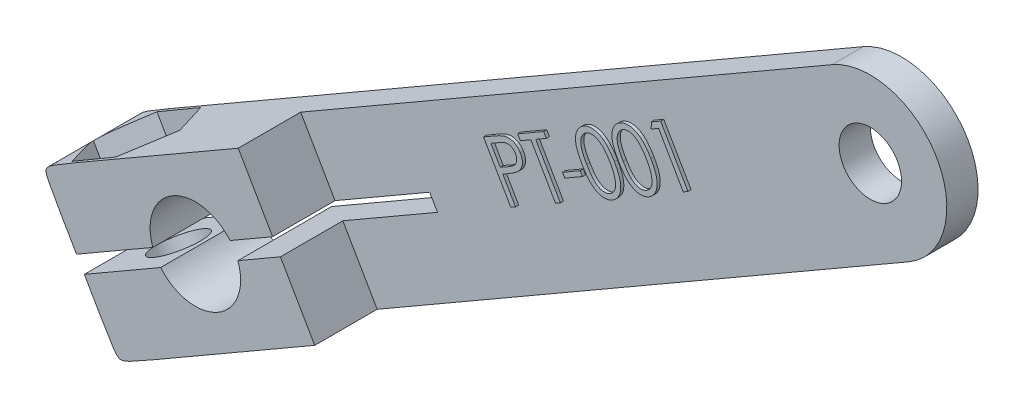
SolidWorks part; units mm, degrees
ref_plane "Piano frontale" through (0, 0, 0) normal (0, 0, 1) x (1, 0, 0)
ref_plane "Piano superiore" through (0, 0, 0) normal (0, 1, 0) x (1, 0, 0)
ref_plane "Piano destro" through (0, 0, 0) normal (1, 0, 0) x (0, 0, -1)
sketch "Schizzo1" plane through (0, 0, 0) normal (0, 0, 1) x (1, 0, 0)
  line L0 (0, 0) -> (0, 55.2) construction
  line L1 (0, 55.2) -> (0, 45.3)
  line L2 (0, 0) -> (39.231, 22.65) construction
  line L3 (0, 45.3) -> (39.231, 22.65) construction
  line L4 (0, 0) -> (39.231, 22.65) construction
  line L5 (-2.45, 4.2435) -> (36.781, 26.8935)
  line L6 (2.45, -4.2435) -> (41.681, 18.4065)
  circle A0 centre (0, 0) radius 2.9
  circle A1 centre (39.231, 22.65) radius 2
  arc A2 (-2.45, 4.2435) -> (2.45, -4.2435) centre (0, 0) ccw
  arc A3 (41.681, 18.4065) -> (36.781, 26.8935) centre (39.231, 22.65) ccw
  point P7 (19.6155, 11.325)
extrude "Estrusione-Estrusione1" add sketch "Schizzo1" along normal blind 2 contours L6 A3 L5 A2 A0 A1 region at (20.1812, 11.6516, 0)
sketch "Schizzo2" plane through (0, 0, 2) normal (0, 0, 1) x (1, 0, 0)
  line L0 (-2.45, 4.2435) -> (-12.8423, -1.7565) construction
  line L1 (-12.8423, -1.7565) -> (-2.45, 4.2435)
  line L2 (-12.8423, -1.7565) -> (-7.9423, -10.2435)
  line L4 (-7.9423, -10.2435) -> (2.45, -4.2435)
  line L5 (41.681, 18.4065) -> (2.45, -4.2435)
  line L6 (41.681, 18.4065) -> (2.45, -4.2435)
  line L7 (-2.45, 4.2435) -> (36.781, 26.8935)
  line L8 (-2.45, 4.2435) -> (36.781, 26.8935)
  line L9 (-2.45, 4.2435) -> (2.7462, 7.2435)
  line L10 (2.7462, 7.2435) -> (7.6462, -1.2435)
  line L11 (7.6462, -1.2435) -> (2.45, -4.2435)
  arc A0 (-2.45, 4.2435) -> (2.45, -4.2435) centre (0, 0) ccw
  arc A2 (41.681, 18.4065) -> (36.781, 26.8935) centre (39.231, 22.65) ccw
  arc A3 (41.681, 18.4065) -> (36.781, 26.8935) centre (39.231, 22.65) ccw
  arc A4 (-2.45, 4.2435) -> (2.45, -4.2435) centre (0, 0) ccw
  point P13 (0, 0)
  point P14 (0, 0)
  circle M11 centre (0, 0) radius 2.9
  line M13 (2.45, -4.2435) -> (41.681, 18.4065)
  arc M16 (-2.45, 4.2435) -> (2.45, -4.2435) centre (0, 0) ccw
extrude "Estrusione-Estrusione2" add sketch "Schizzo2" along normal blind 4 and the other way blind 2 contours L2 L4 L1 M16 | L8 A4 L4 L10 M16 M13 M11 region at (-6.799, -3.9254, 2) region at (0.2354, 5.5923, 2)
sketch "Schizzo3" plane through (0, 0, 6) normal (0, 0, 1) x (1, 0, 0)
  line L0 (0, 0) -> (-10.3923, -6) construction
  line L1 (-12.8423, -1.7565) -> (-7.9423, -10.2435) construction
  line L6 (-10.3923, -6) -> (-10.1423, -6.433)
  line L7 (-10.1423, -6.433) -> (11.5083, 6.067)
  line L8 (-10.1423, -6.433) -> (-10.6423, -5.567)
  line L9 (11.5083, 6.067) -> (11.0083, 6.933)
  line L10 (-10.6423, -5.567) -> (11.0083, 6.933)
  point P11 (0, 0)
  point P12 (0, 0)
  point P13 (0, 0)
  point P14 (0, 0)
  point P15 (0, 0)
  line M9 (-12.8423, -1.7565) -> (-7.9423, -10.2435)
  line M11 (7.6462, -1.2435) -> (2.7462, 7.2435)
  circle M13 centre (0, 0) radius 2.9
extrude "Taglio-Estrusione1" cut sketch "Schizzo3" against normal blind 6 contours L10 L7 L9 M11 | L10 L7 M13 M11 | L0 L7 M13 M9 | L0 L10 M13 M9 region at (-6.3205, -3.9381, 6) region at (-6.5707, -3.5047, 6) region at (3.8475, 2.2214, 6) region at (8.2272, 4.75, 6)
sketch "Schizzo4" plane through (2.45, -4.2435, 0) normal (0.5, -0.866, 0) x (0.866, 0.5, 0)
  line L0 (-12, 3) -> (-5, 3) construction
  line L1 (-12, 0) -> (-12, 6) construction
  circle A0 centre (-5, 3) radius 1.6
extrude "Taglio-Estrusione2" cut sketch "Schizzo4" against normal blind 13
sketch "Schizzo5" plane through (-2.45, 4.2435, 0) normal (-0.5, 0.866, 0) x (0.866, 0.5, 0)
  line L1 (-6.629, -0.2676) -> (-8.1808, -3.0445)
  line L2 (-8.1808, -3.0445) -> (-6.5518, -5.7769)
  line L3 (-6.5518, -5.7769) -> (-3.371, -5.7324)
  line L4 (-3.371, -5.7324) -> (-1.8192, -2.9555)
  line L5 (-1.8192, -2.9555) -> (-3.4482, -0.2231)
  line L6 (-3.4482, -0.2231) -> (-6.629, -0.2676)
  circle A0 centre (-5, -3) radius 3.1811 construction
extrude "Taglio-Estrusione3" cut sketch "Schizzo5" against normal blind 2.4
sketch "Schizzo6" plane through (-10.3923, -6, 0) normal (-0.866, -0.5, 0) x (0, 0, 1)
  line L0 (6, 4.9) -> (6, 0.5)
  line L1 (6, 4.9) -> (6, 0.5)
  line L2 (6, 0.5) -> (2, 0.5)
  line L3 (6, 0.5) -> (2, 0.5)
  line L4 (2, 0.5) -> (2, -0.5)
  line L5 (2, 0.5) -> (2, -0.5)
  line L6 (2, -0.5) -> (6, -0.5)
  line L7 (2, -0.5) -> (6, -0.5)
  line L8 (6, -0.5) -> (6, -4.9)
  line L9 (6, -0.5) -> (6, -4.9)
  line L10 (6, -4.9) -> (2, -4.9)
  line L11 (6, -4.9) -> (2, -4.9)
  line L12 (2, -4.9) -> (0, -4.9)
  line L13 (2, -4.9) -> (0, -4.9)
  line L14 (0, -4.9) -> (0, 4.9)
  line L15 (0, -4.9) -> (0, 4.9)
  line L16 (0, 4.9) -> (2, 4.9)
  line L17 (0, 4.9) -> (2, 4.9)
  line L18 (2, 4.9) -> (6, 4.9)
  line L19 (2, 4.9) -> (6, 4.9)
extrude "Taglio-Estrusione4" cut sketch "Schizzo6" against normal blind 3.5
fillet "Raccordo2" radius 2.5 2 edges at (-4.9112, -8.4935, 3) (-9.8112, -0.0065, 3) conic rho 0.85
sketch "Schizzo7" plane through (0, 0, 2) normal (0, 0, 1) x (1, 0, 0)
  line L0 (11.5083, 6.067) -> (33.159, 18.567) construction
  text T0 "PT-001\r\n"
  point P4 (0, 0)
extrude "Estrusione-Estrusione3" add sketch "Schizzo7" along normal blind 0.2
